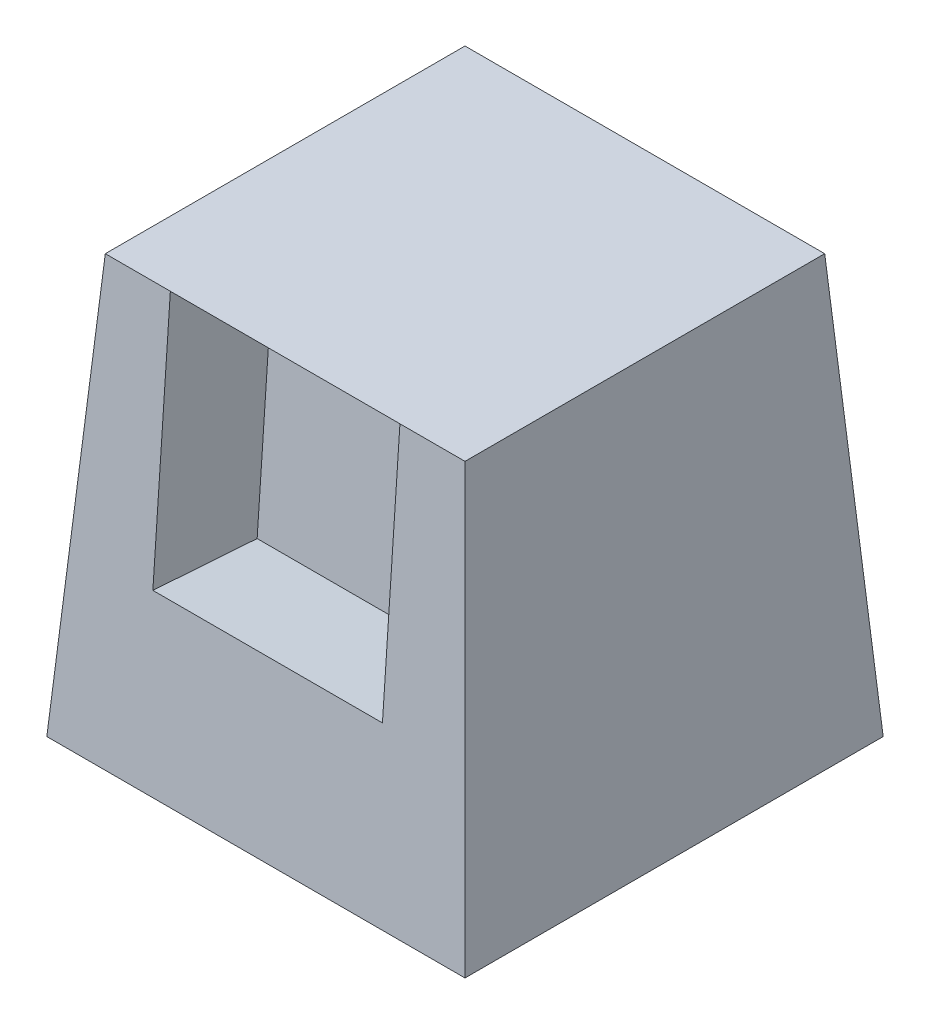
SolidWorks part; units mm, degrees
ref_plane "Front Plane" through (0, 0, 0) normal (0, 0, 1) x (1, 0, 0)
ref_plane "Top Plane" through (0, 0, 0) normal (0, 1, 0) x (1, 0, 0)
ref_plane "Right Plane" through (0, 0, 0) normal (1, 0, 0) x (0, 0, -1)
sketch "Sketch1" plane through (0, 0, 0) normal (0, 1, 0) x (1, 0, 0)
  line L1 (-100, -100) -> (100, -100)
  line L2 (-100, -100) -> (-100, 100)
  line L3 (-100, 100) -> (100, 100)
  line L4 (100, -100) -> (100, 100)
  line L5 (-100, -100) -> (100, 100) construction
  line L6 (-100, 100) -> (100, -100) construction
  point P0 (0, 0)
  dimension "D1" = 200
  dimension "D2" = 200
extrude "Boss-Extrude1" add sketch "Sketch1" along normal blind 200 draft 4 contours L3 L4 L1 L2
sketch "Sketch7" plane through (0, 6.9587, 99.5134) normal (0, 0.0698, 0.9976) x (1, 0, 0)
  line L0 (-86.0146, 193.5127) -> (86.0146, 193.5127) construction
  line L1 (-54.9, 73.5127) -> (54.9, 73.5127)
  line L2 (-54.9, 73.5127) -> (-54.9, 193.5127)
  line L3 (-54.9, 193.5127) -> (54.9, 193.5127)
  line L4 (54.9, 73.5127) -> (54.9, 193.5127)
  line L5 (-54.9, 73.5127) -> (54.9, 193.5127) construction
  line L6 (-54.9, 193.5127) -> (54.9, 73.5127) construction
  line L7 (-86.0146, 205.5129) -> (86.0146, 205.5129) construction
  point P0 (0, 133.5127)
  point P7 (0, 193.5127)
  point P10 (0, 205.5129)
  dimension "D1" = 109.8
  dimension "D2" = 120
extrude "Cut-Extrude2" cut sketch "Sketch7" against normal blind 50
sketch "Sketch12" plane through (0, 6.9587, -99.5134) normal (0, 0.0698, -0.9976) x (-1, 0, 0)
  line L0 (-86.0146, 193.5127) -> (86.0146, 193.5127)
  line L1 (86.0146, 193.5127) -> (100, -6.9756)
  line L2 (100, -6.9756) -> (-100, -6.9756)
  line L3 (-100, -6.9756) -> (-86.0146, 193.5127)
  dimension "D1" = 200
  dimension "D2" = 200.9756
  dimension "D3" = 172.0293
ref_plane "Plane1" through (-100, 0, 100) normal (0, 0, -1) x (-1, 0, 0)
